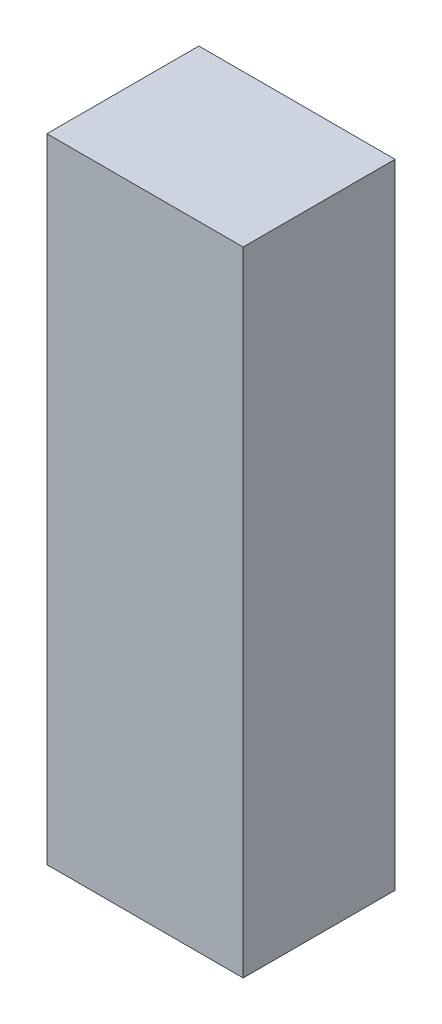
SolidWorks part; units mm, degrees
material "PLA"
ref_plane "Front Plane" through (0, 0, 0) normal (1, 0, 0) x (0, 1, 0)
ref_plane "Top Plane" through (0, 0, 0) normal (0, 0, 1) x (0, 1, 0)
ref_plane "Right Plane" through (0, 0, 0) normal (0, 1, 0) x (-1, 0, 0)
sketch "Sketch1" plane through (0, 0, 0) normal (0, 0, 1) x (0, 1, 0)
  line L1 (-125, -40) -> (125, -40)
  line L2 (-125, -40) -> (-125, 40)
  line L3 (-125, 40) -> (125, 40)
  line L4 (125, -40) -> (125, 40)
  line L5 (-125, -40) -> (125, 40) construction
  line L6 (-125, 40) -> (125, -40) construction
  point P0 (0, 0)
  dimension "D1" = 250
  dimension "D2" = 80
extrude "Boss-Extrude1" add sketch "Sketch1" along normal blind 2.5
sketch "Sketch2" plane through (0, 0, 0) normal (0, 0, -1) x (1, 0, 0)
  line L1 (-40, 125) -> (40, 125) construction
  line L2 (-37.5, -122.5) -> (37.5, -122.5)
  line L3 (-37.5, -122.5) -> (-37.5, 122.5)
  line L4 (-40, -125) -> (40, -125)
  line L5 (40, -125) -> (40, 125)
  line L6 (40, 125) -> (-40, 125)
  line L7 (-40, 125) -> (-40, -125)
  line L8 (-40, -125) -> (40, -125)
  line L9 (40, -125) -> (40, 125)
  line L10 (40, 125) -> (-40, 125)
  line L11 (-40, 125) -> (-40, -125)
  line L12 (-37.5, 122.5) -> (37.5, 122.5)
  line L13 (37.5, -122.5) -> (37.5, 122.5)
  line L14 (-37.5, -122.5) -> (37.5, 122.5) construction
  line L15 (-37.5, 122.5) -> (37.5, -122.5) construction
  point P2 (0, 0)
  dimension "D2" = 2.5
  dimension "D3" = 2.5
extrude "Boss-Extrude2" add sketch "Sketch2" along normal blind 55
sketch "Sketch3" plane through (0, 0, -55) normal (0, 0, -1) x (1, 0, 0)
  line L1 (40, 125) -> (-40, 125)
  line L2 (40, 125) -> (40, -125)
  line L3 (40, -125) -> (-40, -125)
  line L4 (-40, 125) -> (-40, -125)
extrude "Boss-Extrude3" add sketch "Sketch3" along normal blind 2.5
sketch "Sketch4" plane through (-40, 0, 0) normal (-1, 0, 0) x (0, -1, 0)
  line L5 (-125, 2.5) -> (125, 2.5)
  line L6 (-125, 2.5) -> (-125, -57.5)
  line L7 (-125, -57.5) -> (125, -57.5)
  line L8 (125, 2.5) -> (125, -57.5)
extrude "Cut-Extrude1" cut sketch "Sketch4" against normal blind 2.5
equation "\"ball_diameter\"= 3cm"
equation "\"wall_thickness\" = 0.25cm"
equation "\"track_length\" = 25cm"
equation "\"axle\" = 5mm"
equation "\"D1@Sketch1\"=\"track_length\""
equation "\"D1@Boss-Extrude1\"=\"wall_thickness\""
equation "\"D2@Sketch2\"=\"wall_thickness\""
equation "\"D3@Sketch2\"=\"wall_thickness\""
equation "\"D1@Boss-Extrude3\"=\"wall_thickness\""
